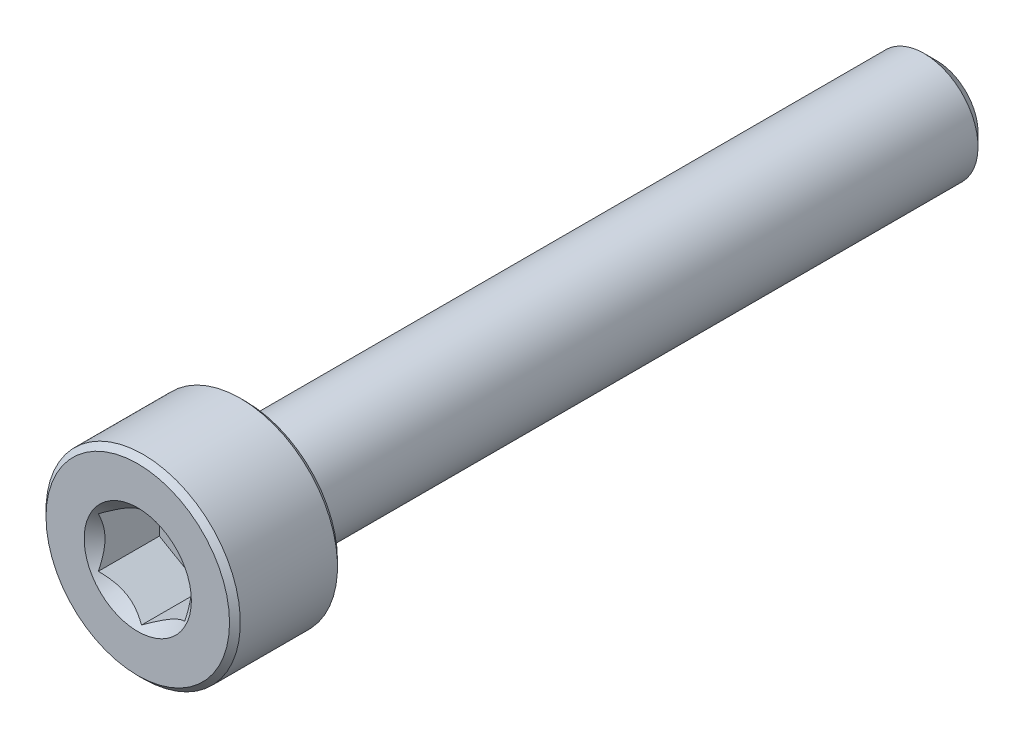
SolidWorks part; units mm, degrees
material "Alloy Steel (SS)"
ref_plane "Front Plane" through (0, 0, 0) normal (0, 0, 1) x (1, 0, 0)
ref_plane "Top Plane" through (0, 0, 0) normal (0, 1, 0) x (1, 0, 0)
ref_plane "Right Plane" through (0, 0, 0) normal (1, 0, 0) x (0, 0, -1)
sketch "Sketch1" plane through (0, 0, 0) normal (1, 0, 0) x (0, 0, -1)
  line L0 (-9.25, 0) -> (9.25, 0) construction
  line L1 (9.25, 0) -> (9.25, 0.9577) construction
  line L2 (9.25, 0.9577) -> (8.9577, 1.25) construction
  line L3 (8.9577, 1.25) -> (8.9125, 1.25) construction
  line L4 (8.9125, 1.25) -> (-6.75, 1.25) construction
  line L5 (-6.75, 1.25) -> (-6.75, 2.25) construction
  line L6 (-6.75, 2.25) -> (-9.25, 2.25) construction
  line L7 (-9.25, 2.25) -> (-9.25, 0) construction
  line L8 (9.25, 0.9577) -> (9.25, 1.25) construction
  line L9 (9.2219, 1.2987) -> (9.4469, 0.909) construction
  line L10 (9.4469, 0.909) -> (9.6719, 1.2987) construction
  line L11 (9.6719, 1.2987) -> (9.2219, 1.2987) construction
  line L12 (9.4469, 1.2987) -> (9.4469, 1.25) construction
  line L13 (9.4469, 0.909) -> (9.4469, 0.9577) construction
  line L14 (9.4187, 0.9577) -> (9.475, 0.9577) construction
  line L15 (9.25, 1.25) -> (9.6437, 1.25) construction
  line L16 (9.2359, 1.2744) -> (9.6578, 1.2744) construction
  line L17 (9.25, 0) -> (9.25, -1.25) construction
  line L18 (-6.875, 2.25) -> (-6.75, 2.125) construction
  line L19 (-9.125, 2.25) -> (-9.25, 2.125) construction
  line L20 (-6.75, 1.25) -> (-6.75, 0) construction
  line L21 (-6.75, 0.625) -> (-1.4167, 0.625) construction
  line L22 (-1.4167, 0.625) -> (3.9167, 0.625) construction
  line L23 (3.9167, 0.625) -> (9.25, 0.625) construction
  line L24 (-1.4167, 0.625) -> (-1.4167, 1.25) construction
  line L25 (-1.4167, 1.25) -> (-1.4167, 2.25) construction
  line L26 (3.9167, 0.625) -> (3.9167, 2.25) construction
  point P0 (-9.25, 1)
  point P3 (8.125, 1.25)
  point P4 (0, 0)
  point P18 (3.9167, 1.25)
  point P22 (9.4469, 0.9577)
  point P24 (8.9125, 1.25)
  point P25 (9.4469, 1.25)
  point P28 (9.4469, 1.2744)
  point P29 (8.125, -1.25)
  point P30 (-1.4167, 1.25)
  point P31 (-8, 2.25)
  point P37 (-7.1875, 2.25)
  point P38 (-9.0625, 2.25)
  point P45 (-1.4167, 0.625)
  point P46 (3.9167, 0.625)
  dimension "D2" = 0.0563
  dimension "D7" = 0.125
  dimension "D8" = 0.125
  dimension "D9" = 0.125
  dimension "D10" = 0.0625
  dimension "D11" = 0.3125
  dimension "Drive Size" = 2
  dimension "Head Diameter" = 4.5
  dimension "Head Height" = 2.5
  dimension "Thread Pitch" = 0.45
  dimension "Thread Dia" = 2.5
  dimension "Length" = 16
  dimension "D12" = 0.3375
  dimension "D4" = 1.125
  dimension "D3" = 45
sketch "Sketch2" plane through (0, 0, 0) normal (1, 0, 0) x (0, 0, -1)
  line L0 (-9.25, 0) -> (-9.25, 2.125)
  line L1 (-9.125, 2.25) -> (-6.875, 2.25)
  line L2 (-6.75, 2.125) -> (-6.75, 1.375)
  line L4 (8.9577, 1.25) -> (9.25, 0.9577)
  line L5 (9.25, 0.9577) -> (9.25, 0)
  line L6 (-6.75, 2.25) -> (-9.25, 2.25) construction
  line L7 (9.25, 0) -> (-9.25, 0)
  line L8 (-9.125, 2.25) -> (-9.25, 2.125) construction
  line L10 (-9.125, 2.25) -> (-9.25, 2.125)
  line L14 (-6.875, 2.25) -> (-6.75, 2.125) construction
  line L16 (-6.875, 2.25) -> (-6.75, 2.125)
  line L17 (-6.75, 1.25) -> (-6.75, 2.25) construction
  line L19 (-6.625, 1.25) -> (8.9577, 1.25)
  line L20 (8.9125, 1.25) -> (-6.75, 1.25) construction
  arc A1 (-6.75, 1.375) -> (-6.625, 1.25) centre (-6.625, 1.375) ccw
  dimension "D3" = 0.125
revolve "Revolve1" add sketch "Sketch2" angle 360 about L7
sketch "Sketch3" plane through (0, 0, 9.25) normal (0, 0, 1) x (1, 0, 0)
  line L1 (1, -0.5774) -> (1, 0.5774)
  line L2 (1, 0.5774) -> (0, 1.1547)
  line L3 (0, 1.1547) -> (-1, 0.5774)
  line L4 (-1, 0.5774) -> (-1, -0.5774)
  line L5 (-1, -0.5774) -> (0, -1.1547)
  line L6 (0, -1.1547) -> (1, -0.5774)
  circle A0 centre (0, 0) radius 1 construction
  circle A1 centre (0, 0) radius 2.25 construction
  circle A2 centre (0, 0) radius 2.25 construction
  circle A3 centre (0, 0) radius 1.1547 construction
  point P13 (0, 0)
  dimension "D1" = 2.3094
extrude "Cut-Extrude1" cut sketch "Sketch3" against normal offset from surface (1.5 mm away) 1 up to face at (0, 2.125, 6.75)
sketch "Sketch4" plane through (0, 0, 9.25) normal (0, 0, 1) x (1, 0, 0)
  circle A0 centre (0, 0) radius 1.2413
  dimension "D1" = 2.4826
extrude "Cut-Extrude2" cut sketch "Sketch4" against normal up to vertex (1.25 mm away) draft 45 up to point (0, 2.25, 8)
sketch "Sketch11" plane through (0, 0, 0) normal (1, 0, 0) x (0, 0, -1)
  line L0 (-9.25, 0) -> (9.25, 0) construction
  line L1 (-9.25, 0) -> (9.25, 0) construction
  line L2 (-3.75, 0) -> (-3.75, 1.25) construction
  line L3 (8.9125, 1.25) -> (-6.75, 1.25) construction
  line L4 (6.25, 0) -> (6.25, 1.25) construction
  line L6 (9.25, 0.9577) -> (9.25, 1.25) construction
  point P2 (-3.75, 0)
  point P3 (6.25, 0)
  dimension "D1" = 3
  dimension "D2" = 3
sketch "Sketch6" [suppressed] plane through (0, 0, -9.25) normal (0, 0, -1) x (-1, 0, 0)
  circle A0 centre (0, 0) radius 1.25
curve "Helix/Spiral1" [suppressed] pitch 0.45 height 16.45 turns 36.5556
sketch "Sketch10" [suppressed] plane through (0, 0, 0) normal (1, 0, 0) x (0, 0, -1)
  line L0 (-6.625, -2.25) -> (-6.625, 2.25)
  line L5 (-9.25, 0) -> (9.25, 0) construction
  line L6 (-6.625, 1.25) -> (-6.625, -1.25) construction
  point P3 (-6.625, 0)
split "Split1" [suppressed] bodies to split 106
sketch "Sketch7" [suppressed] plane through (0, 0, 0) normal (1, 0, 0) x (0, 0, -1)
  line L0 (9.2359, 1.2744) -> (9.6578, 1.2744)
  line L1 (9.6578, 1.2744) -> (9.475, 0.9577)
  line L2 (9.475, 0.9577) -> (9.4187, 0.9577)
  line L3 (9.4187, 0.9577) -> (9.2359, 1.2744)
sweep "Cut-Sweep1" [suppressed] cut profiles "Sketch7" path "Helix/Spiral1"
sketch "Sketch8" [suppressed] plane through (0, 0, 0) normal (1, 0, 0) x (0, 0, -1)
  line L0 (-6.75, 0) -> (-6.75, 1.25)
  line L1 (-6.625, -1.25) -> (-6.625, 1.25) construction
  line L2 (-6.75, 1.25) -> (-6.625, 1.25)
  line L4 (-6.625, 1.25) -> (-5.9033, 0)
  line L5 (-5.9033, 0) -> (-6.75, 0)
  line L6 (8.9125, 1.25) -> (-6.75, 1.25) construction
  line L7 (-9.25, 0) -> (9.25, 0) construction
  dimension "D1" = 60
revolve "Revolve2" [suppressed] add sketch "Sketch8" angle 360 about L5
equation "\"D2@Sketch1\" = \"Thread Pitch@Sketch1\" / 8"
equation "\"D4@Helix/Spiral1\" = \"Thread Pitch@Sketch1\""
equation "\"D7@Sketch1\" = \"Head Height@Sketch1\" * .05"
equation "\"D8@Sketch1\"=\"D7@Sketch1\""
equation "\"D9@Sketch1\"=\"D7@Sketch1\""
equation "\"D10@Sketch1\"=\"D7@Sketch1\"/2"
equation "\"D11@Sketch1\"=\"D10@Sketch1\"*5"
equation "\"D4@Sketch1\"=\"Thread Pitch@Sketch1\"*2.5"
equation "\"D12@Sketch1\"=\"Thread Pitch@Sketch1\"*.75"
equation "\"D3@Helix/Spiral1\"=\"Length@Sketch1\"+\"Thread Pitch@Sketch1\""
equation "\"D3@Sketch2\"=\"Thread Dia@Sketch1\"*0.05"
equation "\"D1@Sketch11\"=\"Length@Sketch1\"*0.1875"
equation "\"D2@Sketch11\"=\"D1@Sketch11\""
equation "\"D1@Sketch4\"=\"D1@Sketch3\"*1.075"
